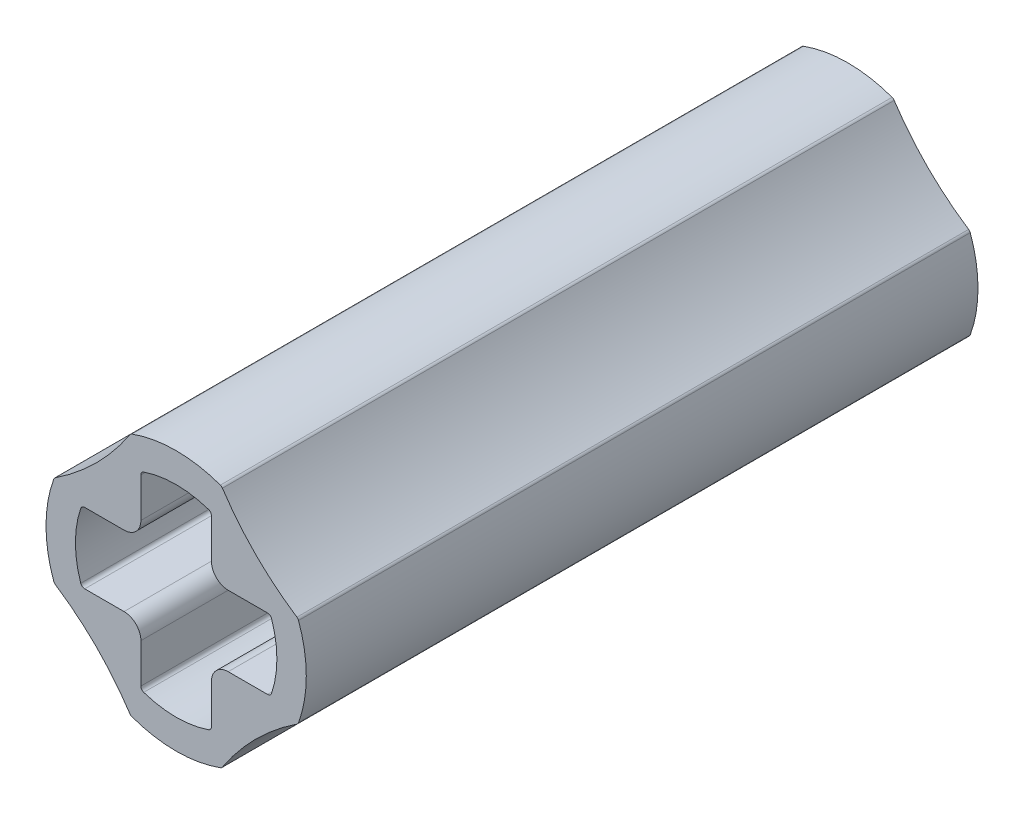
SolidWorks part; units mm, degrees
ref_plane "Front Plane" through (0, 0, 0) normal (0, 0, 1) x (1, 0, 0)
ref_plane "Top Plane" through (0, 0, 0) normal (0, 1, 0) x (1, 0, 0)
ref_plane "Right Plane" through (0, 0, 0) normal (1, 0, 0) x (0, 0, -1)
sketch "Sketch1" plane through (0, 0, 0) normal (0, 0, 1) x (1, 0, 0)
  line L0 (-1.085, -1.085) -> (-1.085, -2.9039)
  line L2 (-1.085, 2.9039) -> (-1.085, 1.085)
  line L4 (1.085, 2.9039) -> (1.085, 1.085)
  line L5 (-1.085, 2.9039) -> (1.085, -2.9039) construction
  line L6 (-1.085, -2.9039) -> (1.085, 2.9039) construction
  line L7 (-2.9039, 1.085) -> (-1.085, 1.085)
  line L9 (-2.9039, -1.085) -> (-1.085, -1.085)
  line L11 (-2.9039, 1.085) -> (2.9039, -1.085) construction
  line L12 (-2.9039, -1.085) -> (2.9039, 1.085) construction
  line L13 (1.085, -1.085) -> (1.085, -2.9039)
  line L14 (1.085, -1.085) -> (2.9039, -1.085)
  line L15 (1.085, 1.085) -> (2.9039, 1.085)
  arc A0 (1.085, 2.9039) -> (-1.085, 2.9039) centre (0, 0) ccw
  arc A1 (-2.9039, 1.085) -> (-2.9039, -1.085) centre (0, 0) ccw
  arc A2 (-1.085, -2.9039) -> (1.085, -2.9039) centre (0, 0) ccw
  arc A3 (2.9039, -1.085) -> (2.9039, 1.085) centre (0, 0) ccw
  dimension "D1" = 6.2
  dimension "D2" = 2.17
  dimension "D3" = 2.17
extrude "Boss-Extrude1" add sketch "Sketch1" along normal blind 16
sketch "Sketch2" plane through (0, 0, 0) normal (0, 0, 1) x (1, 0, 0)
  line L0 (0.84, -0.84) -> (2.2482, -0.84)
  line L2 (-0.84, 2.2482) -> (-0.84, 0.84)
  line L4 (0.84, 2.2482) -> (0.84, 0.84)
  line L5 (-0.84, 2.2482) -> (0.84, -2.2482) construction
  line L6 (-0.84, -2.2482) -> (0.84, 2.2482) construction
  line L7 (-2.2482, 0.84) -> (-0.84, 0.84)
  line L9 (-2.2482, -0.84) -> (-0.84, -0.84)
  line L11 (-2.2482, 0.84) -> (2.2482, -0.84) construction
  line L12 (-2.2482, -0.84) -> (2.2482, 0.84) construction
  line L13 (-0.84, -0.84) -> (-0.84, -2.2482)
  line L14 (0.84, 0.84) -> (2.2482, 0.84)
  line L15 (0.84, -0.84) -> (0.84, -2.2482)
  arc A0 (-2.2482, 0.84) -> (-2.2482, -0.84) centre (0, 0) ccw
  arc A1 (0.84, 2.2482) -> (-0.84, 2.2482) centre (0, 0) ccw
  arc A2 (2.2482, -0.84) -> (2.2482, 0.84) centre (0, 0) ccw
  arc A3 (-0.84, -2.2482) -> (0.84, -2.2482) centre (0, 0) ccw
  dimension "D1" = 4.8
  dimension "D2" = 1.68
  dimension "D3" = 1.68
extrude "Cut-Extrude1" cut sketch "Sketch2" along normal blind 16
fillet "Fillet1" radius 0.4 1 edges at (-0.84, 0.84, 8)
fillet "Fillet2" radius 0.4 1 edges at (0.84, 0.84, 8)
fillet "Fillet3" radius 0.4 1 edges at (0.84, -0.84, 8)
fillet "Fillet4" radius 0.4 1 edges at (-0.84, -0.84, 8)
fillet "Fillet5" radius 6.2 1 edges at (-1.085, 1.085, 8)
fillet "Fillet6" radius 6.2 1 edges at (-1.085, -1.085, 8)
fillet "Fillet7" radius 6.2 1 edges at (1.085, -1.085, 8)
fillet "Fillet8" radius 6.2 1 edges at (1.085, 1.085, 8)
fillet "Fillet9" radius 0.1 1 edges at (0.84, 2.2482, 8)
fillet "Fillet10" radius 0.1 1 edges at (1.085, 2.9039, 8)
fillet "Fillet11" radius 0.1 1 edges at (-1.085, 2.9039, 8)
fillet "Fillet12" radius 0.1 1 edges at (-2.9039, 1.085, 8)
fillet "Fillet13" radius 0.1 1 edges at (-2.9039, -1.085, 8)
fillet "Fillet14" radius 0.1 1 edges at (-1.085, -2.9039, 8)
fillet "Fillet15" radius 0.1 1 edges at (1.085, -2.9039, 8)
fillet "Fillet16" radius 0.1 1 edges at (2.9039, -1.085, 8)
fillet "Fillet17" radius 0.1 1 edges at (2.9039, 1.085, 8)
fillet "Fillet18" radius 0.1 1 edges at (0.84, -2.2482, 8)
fillet "Fillet19" radius 0.1 1 edges at (-0.84, -2.2482, 8)
fillet "Fillet20" radius 0.1 1 edges at (-2.2482, 0.84, 8)
fillet "Fillet21" radius 0.1 1 edges at (-2.2482, -0.84, 8)
fillet "Fillet22" radius 0.1 1 edges at (-0.84, 2.2482, 8)
fillet "Fillet23" radius 0.1 1 edges at (2.2482, -0.84, 8)
fillet "Fillet24" radius 0.1 1 edges at (2.2482, 0.84, 8)
